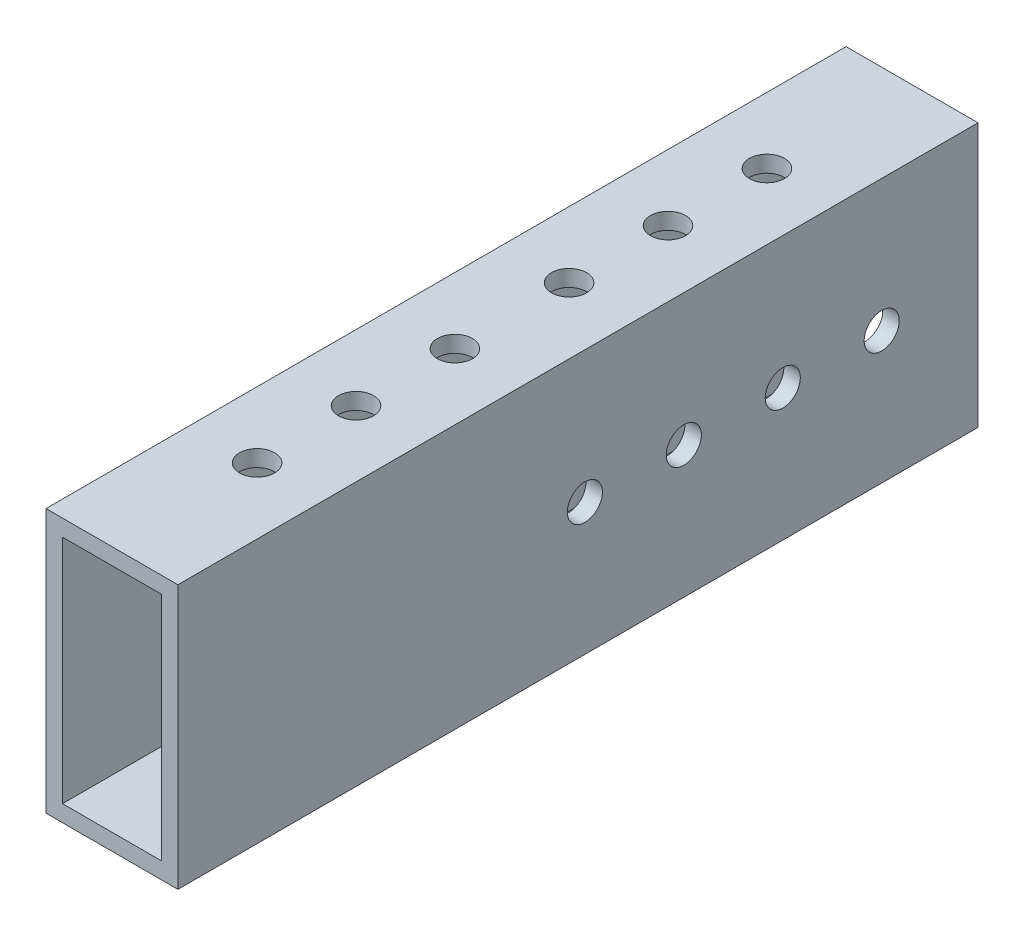
SolidWorks part; units mm, degrees
ref_plane "Front Plane" through (0, 0, 0) normal (0, 0, 1) x (1, 0, 0)
ref_plane "Top Plane" through (0, 0, 0) normal (0, 1, 0) x (1, 0, 0)
ref_plane "Right Plane" through (0, 0, 0) normal (1, 0, 0) x (0, 0, -1)
sketch "Sketch1" plane through (0, 0, 0) normal (0, 0, 1) x (1, 0, 0)
  line L0 (3.175, 47.625) -> (22.225, 47.625)
  line L1 (0, 0) -> (25.4, 0)
  line L2 (0, 0) -> (0, 50.8)
  line L3 (0, 50.8) -> (25.4, 50.8)
  line L4 (25.4, 0) -> (25.4, 50.8)
  line L5 (22.225, 3.175) -> (22.225, 47.625)
  line L6 (3.175, 3.175) -> (22.225, 3.175)
  line L7 (3.175, 3.175) -> (3.175, 47.625)
  dimension "D1" = 50.8
  dimension "D2" = 25.4
  dimension "D3" = 3.175
extrude "Boss-Extrude1" add sketch "Sketch1" along normal blind 154.051
sketch "Sketch2" plane through (0, 50.8, 0) normal (0, 1, 0) x (1, 0, 0)
  line L0 (25.4, -154.051) -> (0, -154.051) construction
  line L1 (0, -154.051) -> (0, 0) construction
  line L3 (0, -77.0255) -> (25.4, -77.0255) construction
  line L4 (25.4, -154.051) -> (25.4, 0) construction
  circle A0 centre (12.7, -126.111) radius 3.3782
  circle A1 centre (12.7, -107.061) radius 3.3782
  circle A2 centre (12.7, -88.011) radius 3.3782
  circle A3 centre (12.7, -27.94) radius 3.3782
  circle A4 centre (12.7, -46.99) radius 3.3782
  circle A5 centre (12.7, -66.04) radius 3.3782
  dimension "D3" = 6.7564
  dimension "D4" = 6.7564
  dimension "D5" = 6.7564
  dimension "D1" = 19.05
  dimension "D2" = 19.05
  dimension "D6" = 27.94
  dimension "D7" = 12.7
  dimension "D8" = 12.7
  dimension "D9" = 12.7
extrude "Cut-Extrude1" cut sketch "Sketch2" against normal through all
sketch "Sketch3" plane through (25.4, 0, 0) normal (1, 0, 0) x (0, 0, -1)
  line L0 (-154.051, 50.8) -> (0, 50.8) construction
  line L1 (0, 0) -> (0, 50.8) construction
  circle A0 centre (-18.542, 25.4) radius 3.3782
  circle A1 centre (-37.592, 25.4) radius 3.3782
  circle A2 centre (-56.642, 25.4) radius 3.3782
  circle A3 centre (-75.692, 25.4) radius 3.3782
  dimension "D1" = 6.7564
  dimension "D2" = 6.7564
  dimension "D3" = 6.7564
  dimension "D4" = 6.7564
  dimension "D5" = 25.4
  dimension "D6" = 25.4
  dimension "D7" = 25.4
  dimension "D8" = 25.4
  dimension "D9" = 18.542
  dimension "D10" = 19.05
  dimension "D11" = 19.05
  dimension "D12" = 19.05
extrude "Cut-Extrude2" cut sketch "Sketch3" against normal through all
